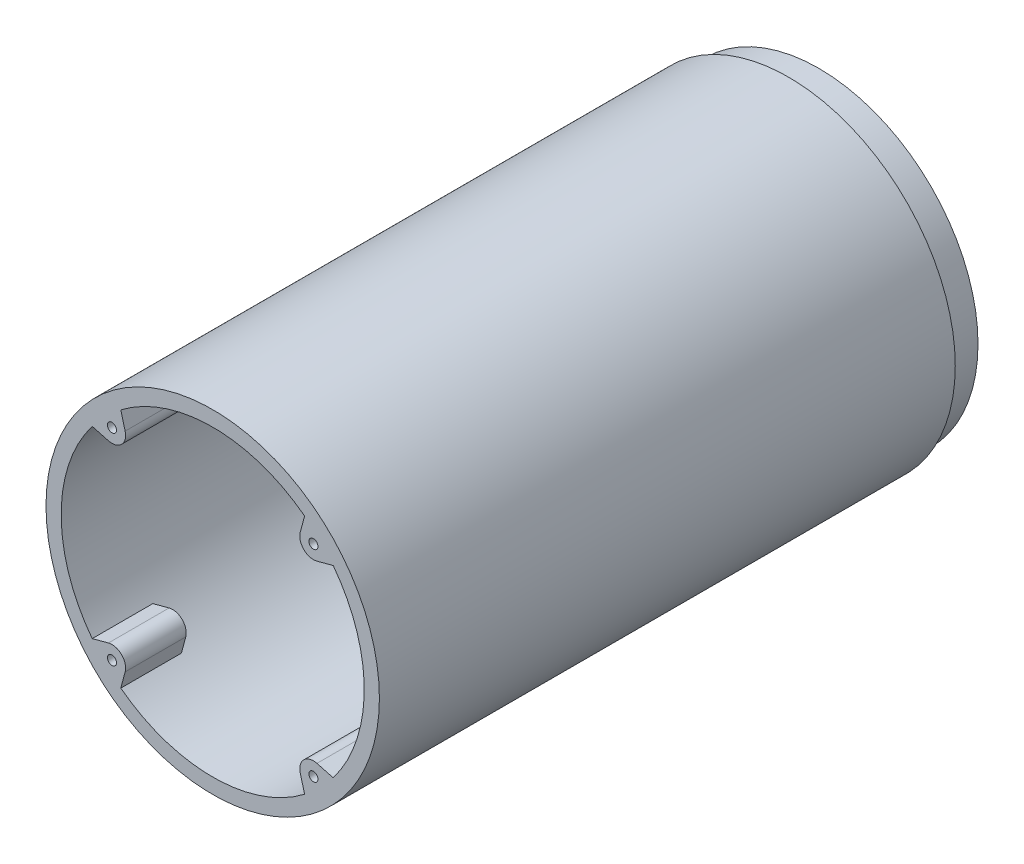
SolidWorks part; units mm, degrees
ref_plane "前视基准面" through (0, 0, 0) normal (0, 0, 1) x (1, 0, 0)
ref_plane "上视基准面" through (0, 0, 0) normal (0, 1, 0) x (1, 0, 0)
ref_plane "右视基准面" through (0, 0, 0) normal (1, 0, 0) x (0, 0, -1)
sketch "草图2" plane through (0, 0, 0) normal (0, 0, 1) x (1, 0, 0)
  circle A0 centre (0, 0) radius 55
  circle A1 centre (0, 0) radius 50
  dimension "D1" = 100
  dimension "D2" = 110
extrude "凸台-拉伸1" add sketch "草图2" along normal blind 200
sketch "草图1" plane through (0, 0, 0) normal (0, 0, 1) x (1, 0, 0)
  line L0 (0, 0) -> (-25.5751, 0) construction
  line L1 (-49.5531, 6.6702) -> (-44.75, 3.8971)
  line L2 (-49.5531, -6.6702) -> (-44.75, -3.8971)
  line L3 (0, 0) -> (-6.6702, 49.5531) construction
  line L4 (-49.5531, -6.6702) -> (0, 0) construction
  line L5 (6.6702, 49.5531) -> (3.8971, 44.75)
  line L6 (-6.6702, 49.5531) -> (-3.8971, 44.75)
  line L7 (49.5531, -6.6702) -> (44.75, -3.8971)
  line L8 (49.5531, 6.6702) -> (44.75, 3.8971)
  line L9 (-6.6702, -49.5531) -> (-3.8971, -44.75)
  line L10 (6.6702, -49.5531) -> (3.8971, -44.75)
  circle A0 centre (0, 0) radius 50 construction
  circle A1 centre (0, 0) radius 55
  circle A2 centre (-47, 0) radius 1.5
  arc A4 (-44.75, 3.8971) -> (-44.75, -3.8971) centre (-47, 0) cw
  arc A5 (-49.5531, 6.6702) -> (-6.6702, 49.5531) centre (0, 0) cw
  circle A6 centre (0, 47) radius 1.5
  arc A7 (3.8971, 44.75) -> (-3.8971, 44.75) centre (0, 47) cw
  arc A8 (6.6702, 49.5531) -> (49.5531, 6.6702) centre (0, 0) cw
  circle A9 centre (47, 0) radius 1.5
  arc A10 (44.75, -3.8971) -> (44.75, 3.8971) centre (47, 0) cw
  arc A11 (49.5531, -6.6702) -> (6.6702, -49.5531) centre (0, 0) cw
  circle A12 centre (0, -47) radius 1.5
  arc A13 (-3.8971, -44.75) -> (3.8971, -44.75) centre (0, -47) cw
  arc A14 (-6.6702, -49.5531) -> (-49.5531, -6.6702) centre (0, 0) cw
  circle A15 centre (0, 0) radius 50 construction
  circle A16 centre (0, 0) radius 55 construction
  point P38 (0, 0)
  dimension "D3" = 47
  dimension "D4" = 3
  dimension "D5" = 3
  dimension "D7" = 90
  dimension "D8" = 4
  dimension "D6" = 30
extrude "凸台-拉伸2" add sketch "草图1" along normal blind 20 contours A1 A12 A9 A6 A2 L9 A14 L2 A4 L1 A5 L6 A7 L5 A8 L8 A10 L7 A11 L10 A13 region at (-53.4444, 0, 0)
sketch "草图3" plane through (0, 0, 20) normal (0, 0, 1) x (1, 0, 0)
  line L0 (-1.5877, 44.25) -> (1.5877, 44.25)
  line L1 (-44.25, -1.5877) -> (-44.25, 1.5877)
  line L2 (-44.25, 1.5877) -> (-47, 3.1754)
  line L3 (-47, 3.1754) -> (-49.75, 1.5877)
  line L4 (-49.75, 1.5877) -> (-49.75, -1.5877)
  line L5 (-49.75, -1.5877) -> (-47, -3.1754)
  line L6 (-47, -3.1754) -> (-44.25, -1.5877)
  line L7 (1.5877, 44.25) -> (3.1754, 47)
  line L8 (3.1754, 47) -> (1.5877, 49.75)
  line L9 (1.5877, 49.75) -> (-1.5877, 49.75)
  line L10 (-1.5877, 49.75) -> (-3.1754, 47)
  line L11 (-3.1754, 47) -> (-1.5877, 44.25)
  line L12 (44.25, 1.5877) -> (44.25, -1.5877)
  line L13 (44.25, -1.5877) -> (47, -3.1754)
  line L14 (47, -3.1754) -> (49.75, -1.5877)
  line L15 (49.75, -1.5877) -> (49.75, 1.5877)
  line L16 (49.75, 1.5877) -> (47, 3.1754)
  line L17 (47, 3.1754) -> (44.25, 1.5877)
  line L18 (1.5877, -44.25) -> (-1.5877, -44.25)
  line L19 (-1.5877, -44.25) -> (-3.1754, -47)
  line L20 (-3.1754, -47) -> (-1.5877, -49.75)
  line L21 (-1.5877, -49.75) -> (1.5877, -49.75)
  line L22 (1.5877, -49.75) -> (3.1754, -47)
  line L23 (3.1754, -47) -> (1.5877, -44.25)
  circle A0 centre (-47, 0) radius 2.75 construction
  circle A1 centre (0, 47) radius 2.75 construction
  circle A2 centre (47, 0) radius 2.75 construction
  circle A3 centre (0, -47) radius 2.75 construction
  point P36 (0, 0)
  dimension "D1" = 5.5
  dimension "D2" = 4
extrude "切除-拉伸1" cut sketch "草图3" against normal blind 2
ref_plane "基准面4" through (0, 0, 100) normal (0, 0, -1) x (-1, 0, 0)
sketch "草图4" plane through (0, 0, 0) normal (0, 0, -1) x (-1, 0, 0)
  circle A0 centre (0, 0) radius 55
  circle A1 centre (0, 0) radius 52.5
  circle A2 centre (0, 0) radius 55 construction
  dimension "D1" = 2.5
extrude "切除-拉伸2" cut sketch "草图4" against normal blind 10
sketch "草图5" plane through (0, 0, 0) normal (0, 0, 1) x (1, 0, 0)
  line L0 (0, 0) -> (-16.1279, 16.1279) construction
  line L1 (-30.3228, 39.7559) -> (-28.8874, 34.3987)
  line L2 (-39.7559, 30.3228) -> (-34.3987, 28.8874)
  line L3 (0, 0) -> (30.3228, 39.7559) construction
  line L4 (-39.7559, 30.3228) -> (0, 0) construction
  line L5 (39.7559, 30.3228) -> (34.3987, 28.8874)
  line L6 (30.3228, 39.7559) -> (28.8874, 34.3987)
  line L7 (30.3228, -39.7559) -> (28.8874, -34.3987)
  line L8 (39.7559, -30.3228) -> (34.3987, -28.8874)
  line L9 (-39.7559, -30.3228) -> (-34.3987, -28.8874)
  line L10 (-30.3228, -39.7559) -> (-28.8874, -34.3987)
  line L11 (0, 0) -> (-100.2667, 0) construction
  circle A0 centre (0, 0) radius 50 construction
  circle A1 centre (0, 0) radius 55
  circle A2 centre (-33.234, 33.234) radius 1.5
  arc A4 (-28.8874, 34.3987) -> (-34.3987, 28.8874) centre (-33.234, 33.234) cw
  arc A5 (-30.3228, 39.7559) -> (30.3228, 39.7559) centre (0, 0) cw
  circle A6 centre (33.234, 33.234) radius 1.5
  arc A7 (34.3987, 28.8874) -> (28.8874, 34.3987) centre (33.234, 33.234) cw
  arc A8 (39.7559, 30.3228) -> (39.7559, -30.3228) centre (0, 0) cw
  circle A9 centre (33.234, -33.234) radius 1.5
  arc A10 (28.8874, -34.3987) -> (34.3987, -28.8874) centre (33.234, -33.234) cw
  arc A11 (30.3228, -39.7559) -> (-30.3228, -39.7559) centre (0, 0) cw
  circle A12 centre (-33.234, -33.234) radius 1.5
  arc A13 (-34.3987, -28.8874) -> (-28.8874, -34.3987) centre (-33.234, -33.234) cw
  arc A14 (-39.7559, -30.3228) -> (-39.7559, 30.3228) centre (0, 0) cw
  point P14 (0, 0)
  point P16 (0, 0)
  point P38 (0, 0)
  dimension "D1" = 100
  dimension "D2" = 110
  dimension "D3" = 47
  dimension "D4" = 3
  dimension "D5" = 3
  dimension "D7" = 90
  dimension "D8" = 4
  dimension "D6" = 30
  dimension "D9" = 45
extrude "凸台-拉伸3" add sketch "草图5" against normal blind 20 from surface contours A1 A12 A9 A6 A2 L9 A14 L2 A4 L1 A5 L6 A7 L5 A8 L8 A10 L7 A11 L10 A13 region at (-53.4444, 0, 0) starting at face at (55, 0, 200)
sketch "草图6" plane through (0, 0, 0) normal (0, 0, 1) x (1, 0, 0)
  line L24 (0, 0) -> (-58.0423, 58.0423) construction
  line L25 (0, 0) -> (-90.9216, 0) construction
  line L26 (36.3012, 34.0559) -> (34.0559, 36.3012)
  line L27 (-34.0559, 36.3012) -> (-36.3012, 34.0559)
  line L28 (-36.3012, 34.0559) -> (-35.4794, 30.9887)
  line L29 (-35.4794, 30.9887) -> (-32.4122, 30.1668)
  line L30 (-32.4122, 30.1668) -> (-30.1668, 32.4122)
  line L31 (-30.1668, 32.4122) -> (-30.9887, 35.4794)
  line L32 (-30.9887, 35.4794) -> (-34.0559, 36.3012)
  line L33 (34.0559, 36.3012) -> (30.9887, 35.4794)
  line L34 (30.9887, 35.4794) -> (30.1668, 32.4122)
  line L35 (30.1668, 32.4122) -> (32.4122, 30.1668)
  line L36 (32.4122, 30.1668) -> (35.4794, 30.9887)
  line L37 (35.4794, 30.9887) -> (36.3012, 34.0559)
  line L38 (34.0559, -36.3012) -> (36.3012, -34.0559)
  line L39 (36.3012, -34.0559) -> (35.4794, -30.9887)
  line L40 (35.4794, -30.9887) -> (32.4122, -30.1668)
  line L41 (32.4122, -30.1668) -> (30.1668, -32.4122)
  line L42 (30.1668, -32.4122) -> (30.9887, -35.4794)
  line L43 (30.9887, -35.4794) -> (34.0559, -36.3012)
  line L44 (-36.3012, -34.0559) -> (-34.0559, -36.3012)
  line L45 (-34.0559, -36.3012) -> (-30.9887, -35.4794)
  line L46 (-30.9887, -35.4794) -> (-30.1668, -32.4122)
  line L47 (-30.1668, -32.4122) -> (-32.4122, -30.1668)
  line L48 (-32.4122, -30.1668) -> (-35.4794, -30.9887)
  line L49 (-35.4794, -30.9887) -> (-36.3012, -34.0559)
  circle A1 centre (-33.234, 33.234) radius 2.75 construction
  point P5 (0, 0)
  point P33 (0, 0)
  dimension "D1" = 45
  dimension "D3" = 4
  dimension "D2" = 5.5
extrude "切除-拉伸3" cut sketch "草图6" along normal blind 2.5 from surface starting at face at (-33.0224, -33.0224, 180)
